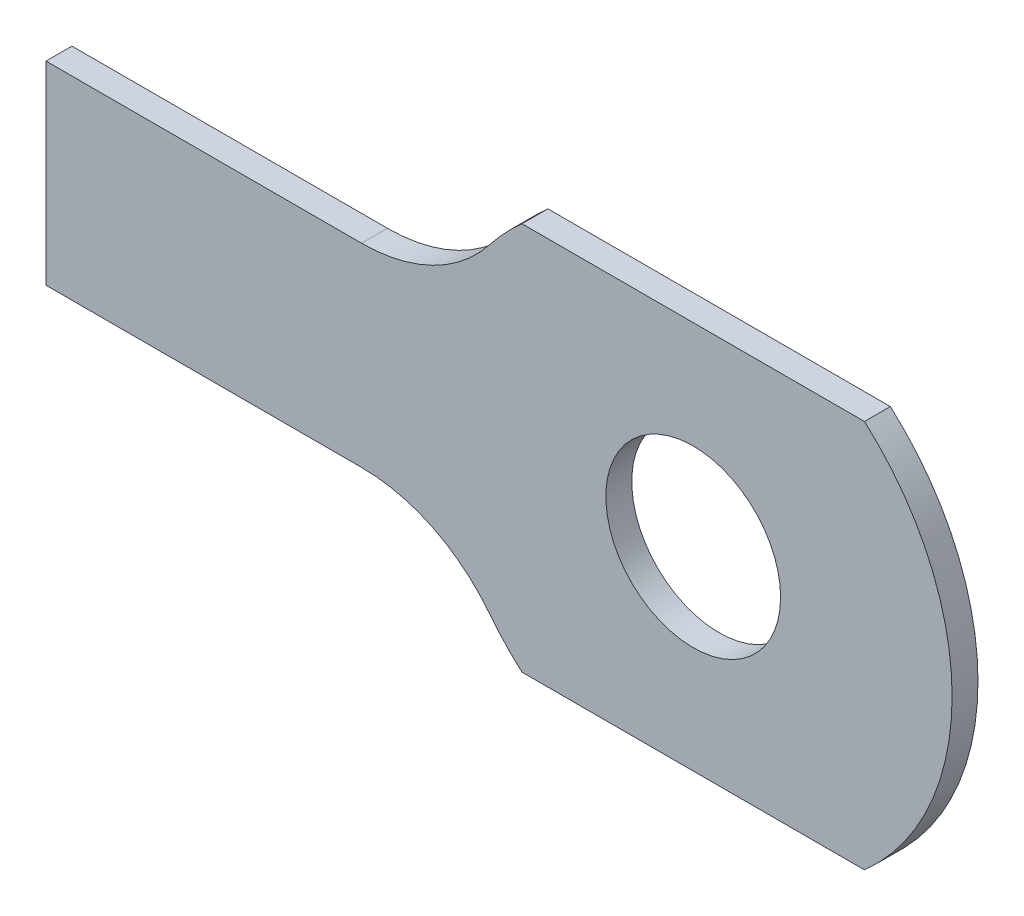
SolidWorks part; units mm, degrees
ref_plane "Front" through (0, 0, 0) normal (0, 0, 1) x (1, 0, 0)
ref_plane "Top" through (0, 0, 0) normal (0, 1, 0) x (1, 0, 0)
ref_plane "Right" through (0, 0, 0) normal (1, 0, 0) x (0, 0, -1)
sketch "Sketch1" plane through (0, 0, 0) normal (0, 0, 1) x (1, 0, 0)
  line L0 (-2.6458, 3) -> (2.6458, 3)
  line L1 (-2.6458, -3) -> (2.6458, -3)
  line L2 (-10, 1.5) -> (-5.1235, 1.5)
  line L3 (-10, -1.5) -> (-5.1235, -1.5)
  line L4 (-5.8264, 0) -> (6.0158, 0) construction
  line L5 (-10, 1.5) -> (-10, -1.5)
  arc A0 (-2.6458, 3) -> (-3.1529, 2.4615) centre (0, 0) ccw
  circle A1 centre (0, 0) radius 1.35
  arc A2 (2.6458, -3) -> (2.6458, 3) centre (0, 0) ccw
  arc A3 (-5.1235, 1.5) -> (-3.1529, 2.4615) centre (-5.1235, 4) ccw
  arc A4 (-3.1529, -2.4615) -> (-2.6458, -3) centre (0, 0) ccw
  arc A5 (-5.1235, -1.5) -> (-3.1529, -2.4615) centre (-5.1235, -4) cw
  dimension "D2" = 3
extrude "Base-Extrude" add sketch "Sketch1" against normal blind 0.4
equation "\"D2@Sketch1\" = \"B1@Sketch1\" / 2"
